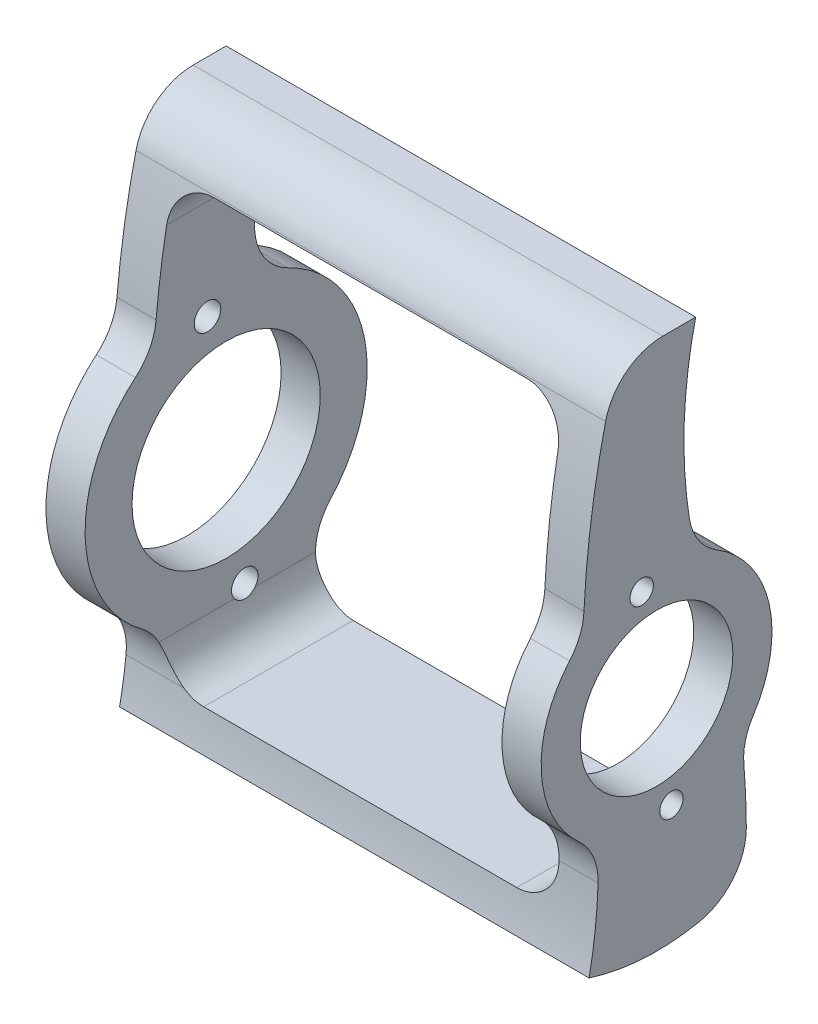
SolidWorks part; units mm, degrees
other "Markup2"
sketch "Sketch9" plane through (31.75, 50.4016, 20.35) normal (0.8402, 0.4575, 0.2911) x (0.3274, 0, -0.9449)
material "AISI 4340 Steel, normalized"
ref_plane "Front Plane" through (0, 0, 0) normal (0, 0, 1) x (1, 0, 0)
ref_plane "Top Plane" through (0, 0, 0) normal (0, 1, 0) x (1, 0, 0)
ref_plane "Right Plane" through (0, 0, 0) normal (1, 0, 0) x (0, 0, -1)
other "Center of Mass"
sketch "Weapon Layout" plane through (0, 0, 0) normal (1, 0, 0) x (0, 0, -1)
  line L0 (-6.35, 50.4016) -> (6.35, 50.4016) construction
  line L1 (-10.9443, -33.834) -> (14.4209, -32.5046) construction
  line L2 (6.35, 50.4016) -> (-5.4537, 0) construction
  line L3 (6.35, 50.4016) -> (0, 0) construction
  line L4 (0, 0) -> (0, -33.2604) construction
  circle A0 centre (0, 0) radius 14 construction
  circle A1 centre (0, 0) radius 50.8 construction
  circle A2 centre (0, 0) radius 17.175 construction
  circle A3 centre (0, 0) radius 20.35 construction
  arc A4 (-6.35, 50.4016) -> (-20.35, 0) centre (77.3756, 0) ccw construction
  arc A5 (23.3803, -26.7932) -> (-23.7089, -26.5029) centre (0, 0) cw construction
  arc A6 (6.35, 50.4016) -> (15.4347, 13.2625) centre (47.4536, 40.7754) ccw construction
  dimension "D1" = 28
  dimension "D2" = 101.6
  dimension "D3" = 3.175
  dimension "D4" = 6.35
  dimension "D5" = 12.7
  dimension "D7" = 6
  dimension "D6" = 15.24
  dimension "D8" = 25.4
  dimension "D9" = 87
sketch "Sketch2" plane through (0, 0, 0) normal (1, 0, 0) x (0, 0, -1)
  line L0 (-6.35, 50.4016) -> (6.35, 50.4016)
  line L1 (-11.3249, -1.5462) -> (0, 0) construction
  line L2 (6.35, 50.4016) -> (-5.4537, 0) construction
  line L3 (-11.5714, 0.7977) -> (-15.24, 50.4016) construction
  arc A0 (-10.9443, -33.834) -> (14.4209, -32.5046) centre (0, 0) ccw
  arc A1 (-23.7089, -26.5029) -> (23.3803, -26.7932) centre (0, 0) ccw construction
  arc A2 (-10.934, -3.8704) -> (-11.5714, 0.7977) centre (26.4248, 3.6078) cw
  arc A3 (9.7952, 6.5275) -> (11.7704, 0.1087) centre (-25.4904, -7.8439) cw
  arc A4 (-11.5714, 0.7977) -> (-6.35, 50.4016) centre (128.3504, 11.1461) cw
  arc A5 (-10.934, -3.8704) -> (-10.9443, -33.834) centre (-85.6518, -18.8267) cw
  arc A6 (6.35, 50.4016) -> (9.7952, 6.5275) centre (76.9323, 33.8717) ccw
  arc A7 (11.7704, 0.1087) -> (14.4209, -32.5046) centre (-112.4323, -26.3999) cw
  circle A9 centre (0, 0) radius 11.43 construction
  point P25 (10.9245, 3.3617)
  dimension "D1" = 127
  dimension "D2" = 38.1
  dimension "D3" = 76.2
  dimension "D4" = 38.1
  dimension "D5" = 22.86
  dimension "D6" = 8.89
extrude "Boss-Extrude2" add sketch "Sketch2" along normal mid plane 76.2
sketch "Sketch3" plane through (0, 0, 0) normal (0, 0, 1) x (1, 0, 0)
  line L0 (38.1, 50.4016) -> (-38.1, 50.4016) construction
  line L1 (-31.75, 42.7816) -> (31.75, 42.7816)
  line L2 (-31.75, 42.7816) -> (-31.75, -27.94)
  line L3 (-31.75, -27.94) -> (31.75, -27.94)
  line L4 (31.75, 42.7816) -> (31.75, -27.94)
  line L6 (-38.1, -35.56) -> (38.1, -35.56) construction
  line L7 (-38.1, 50.4016) -> (-38.1, 0.7977) construction
  dimension "D1" = 7.62
  dimension "D3" = 6.35
  dimension "D4" = 7.62
  dimension "D2" = 6.35
extrude "Cut-Extrude1" cut sketch "Sketch3" against normal through all both and the other way through all
fillet "Fillet1" radius 6.35 4 edges at (-31.75, 42.7816, 1.6753) (31.75, 42.7816, 1.6753) (31.75, -27.94, -2.2798) (-31.75, -27.94, -2.2798)
fillet "Fillet3" radius 9.525 2 edges at (0, -32.5046, -14.4209) (0, 50.4016, 6.35)
sketch "Sketch6" plane through (-38.1, 0, 0) normal (-1, 0, 0) x (0, 0, 1)
  circle A0 centre (0, 0) radius 22.89
  dimension "D1" = 45.78
extrude "Boss-Extrude3" add sketch "Sketch6" against normal up to surface (6.35 mm away) up to face at (-31.75, 4.1451, 0.3502)
sketch "Sketch7" plane through (-38.1, 0, 0) normal (-1, 0, 0) x (0, 0, 1)
  circle A0 centre (0, 0) radius 15.27
  arc A1 (9.4783, -20.8354) -> (11.6939, 19.6775) centre (0, 0) ccw construction
  dimension "D1" = 30.54
extrude "Cut-Extrude3" cut sketch "Sketch7" against normal up to next
sketch "Sketch10" plane through (38.1, 0, 0) normal (1, 0, 0) x (0, 0, -1)
  circle A0 centre (0, 0) radius 18.7325
  dimension "D1" = 37.465
extrude "Boss-Extrude4" add sketch "Sketch10" against normal up to surface (6.35 mm away) up to face at (31.75, 4.1451, 0.3502)
sketch "Sketch5" plane through (38.1, 0, 0) normal (1, 0, 0) x (0, 0, -1)
  circle A0 centre (0, 0) radius 12.3825
  circle A1 centre (0, 0) radius 6.35 construction
  dimension "D1" = 12.7
  dimension "D2" = 24.765
extrude "Cut-Extrude2" cut sketch "Sketch5" against normal up to next
fillet "Fillet2" radius 9.525 8 edges at (-34.925, 19.6775, 11.6939) (-34.925, -20.8354, 9.4783) (-34.925, -17.8878, -14.2821) (-34.925, 22.2493, -5.378) (34.925, 17.6489, -6.2788) (34.925, -12.645, -13.8207) (34.925, -16.1454, 9.499) (34.925, 14.4551, 11.9145)
sketch "Sketch11" plane through (38.1, 0, 0) normal (1, 0, 0) x (0, 0, -1)
  circle A0 centre (-2.4136, 16.1721) radius 1.8986
  circle A1 centre (-2.4136, 16.1721) radius 1.8986 construction
  circle A2 centre (2.4136, -16.1721) radius 1.8987
  circle A3 centre (2.4136, -16.1721) radius 1.8986 construction
extrude "Cut-Extrude4" cut sketch "Sketch11" against normal up to surface (6.35 mm away) up to face at (31.75, 12.3825, 0)
hole_wizard "#6 Clearance Hole1" positions "Sketch12" profile "Sketch13" hole size "#6" standard "ANSI Inch"
sketch "Sketch12" plane through (-38.1, 0, 0) normal (1, 0, 0) x (0, 0, -1)
  point P0 (-3.0235, 20.259)
  point P3 (3.0235, -20.259)
sketch "Sketch13" plane through (-38.1, 20.259, 3.0235) normal (0, 1, 0) x (0, 0, 1)
  line L0 (0, 0) -> (0, 8.9134)
  line L1 (0, 8.9134) -> (2.1526, 7.62)
  line L2 (2.1526, 7.62) -> (2.1526, 0)
  line L5 (2.1526, 0) -> (0, 0)
  line L10 (0, 8.9134) -> (-2.1527, 7.62) construction
  line L11 (0, -6.35) -> (0, 107.95) construction
  dimension "Hole Dia." = 4.3053
  dimension "Hole Depth" = 7.62
  dimension "Drill Angle" = 118
equation "\"D1@Weapon Layout\" = 28mm"
equation "\"D1@Sketch6\"=\"bearing OD L\"+1/2in+0.2in"
equation "\"D2@Sketch3\"=\"D3@Sketch3\""
equation "\"D1@Sketch7\"=\"bearing OD L\"+0.1in"
equation "\"D2@Sketch5\"=\"bearing OD R\" + .1"
equation "\"D1@Sketch10\"=\"bearing OD R\" + 1/2 + .1"
equation "\"bearing OD R\"= 7 / 8"
equation "\"bearing OD L\"= 28mm"
